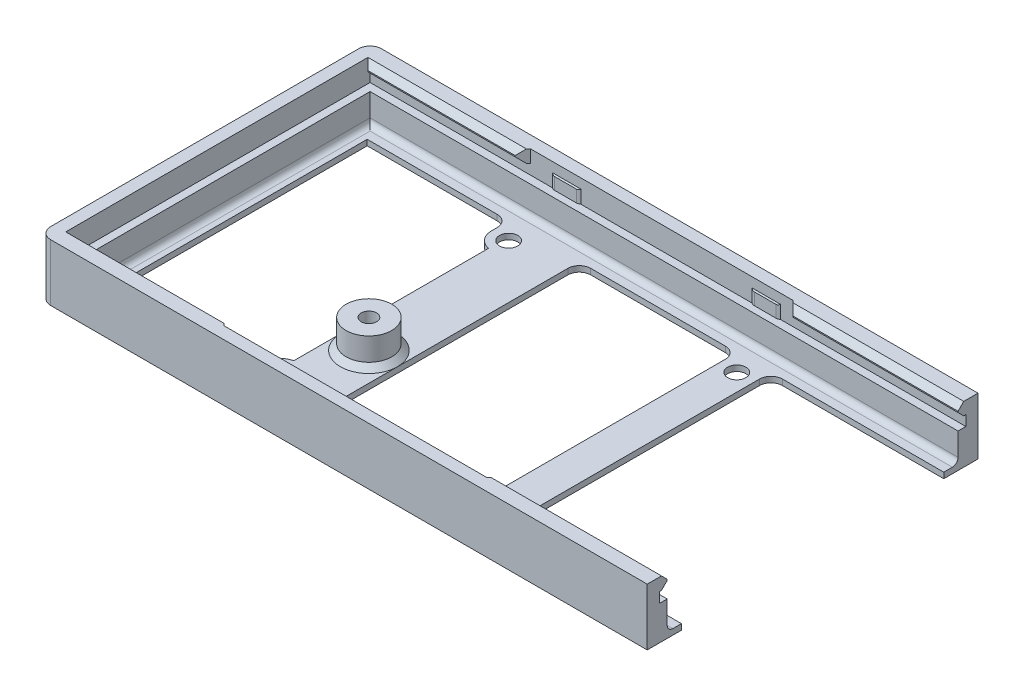
SolidWorks part; units mm, degrees
other "Cámara1"
ref_plane "Alzado" through (0, 0, 0) normal (0, 0, 1) x (1, 0, 0)
ref_plane "Planta" through (0, 0, 0) normal (0, 1, 0) x (1, 0, 0)
ref_plane "Vista lateral" through (0, 0, 0) normal (1, 0, 0) x (0, 0, -1)
sketch "Croquis1" plane through (0, 0, 0) normal (0, 1, 0) x (1, 0, 0)
  line L0 (-23, 20) -> (-23, 23)
  line L1 (47.8, -23) -> (23, -23)
  line L2 (47.8, -23) -> (47.8, 23)
  line L3 (47.8, 23) -> (23, 23)
  line L4 (-47.8, -23) -> (-47.8, 23)
  line L5 (47.8, -23) -> (-47.8, 23) construction
  line L6 (47.8, 23) -> (-47.8, -23) construction
  line L7 (53.3, -29) -> (-53.3, -29)
  line L8 (53.3, -29) -> (53.3, 29)
  line L9 (53.3, 29) -> (-53.3, 29)
  line L10 (-53.3, -29) -> (-53.3, 29)
  line L11 (53.3, -29) -> (-53.3, 29) construction
  line L12 (53.3, 29) -> (-53.3, -29) construction
  line L13 (-17, 20) -> (-17, 23)
  line L14 (-23, 23) -> (-47.8, 23)
  line L15 (0, 0) -> (0, 23) construction
  line L16 (0, 0) -> (-47.8, 0) construction
  line L17 (17, 20) -> (17, 23)
  line L18 (23, 20) -> (23, 23)
  line L19 (23, -20) -> (23, -23)
  line L20 (17, -20) -> (17, -23)
  line L21 (-17, -20) -> (-17, -23)
  line L22 (-23, -20) -> (-23, -23)
  line L23 (-23, -23) -> (-47.8, -23)
  line L24 (17, -23) -> (-17, -23)
  line L25 (17, 23) -> (-17, 23)
  circle A0 centre (-20, 20) radius 1.6
  arc A1 (-23, 20) -> (-17, 20) centre (-20, 20) ccw
  arc A2 (23, 20) -> (17, 20) centre (20, 20) cw
  circle A3 centre (20, 20) radius 1.6
  circle A4 centre (20, -20) radius 1.6
  arc A5 (23, -20) -> (17, -20) centre (20, -20) ccw
  arc A6 (-23, -20) -> (-17, -20) centre (-20, -20) cw
  circle A7 centre (-20, -20) radius 1.6
  point P0 (0, 0)
  point P6 (0, 0)
  dimension "D5" = 3.2
  dimension "D6" = 40
  dimension "D7" = 40
  dimension "D1" = 106.6
  dimension "D2" = 58
  dimension "D3" = 5.5
  dimension "D4" = 6
extrude "Saliente-Extruir1" add sketch "Croquis1" along normal blind 1
fillet "Redondeo1" radius 2 8 edges at (-23, 0.5, 23) (23, 0.5, 23) (17, 0.5, 23) (-17, 0.5, 23) (23, 0.5, -23) (17, 0.5, -23) (-17, 0.5, -23) (-23, 0.5, -23)
sketch "Croquis2" plane through (0, 1, 0) normal (0, 1, 0) x (1, 0, 0)
  line L0 (53.3, -25.5) -> (53.3, -29)
  line L1 (-53.3, 29) -> (53.3, 29)
  line L2 (-53.3, 29) -> (-53.3, -29)
  line L3 (-53.3, -29) -> (53.3, -29)
  line L4 (53.3, 29) -> (53.3, 25.5)
  line L5 (53.3, -25.5) -> (-49.8, -25.5)
  line L7 (53.3, 25.5) -> (-49.8, 25.5)
  line L8 (-49.8, -25.5) -> (-49.8, 25.5)
  point P6 (0, 0)
  dimension "D1" = 3.5
  dimension "D2" = 3.5
  dimension "D3" = 3.5
extrude "Saliente-Extruir2" add sketch "Croquis2" along normal blind 9
sketch "Croquis3" plane through (53.3, 0, 0) normal (1, 0, 0) x (0, 0, -1)
  line L1 (26.87, 6) -> (-26.87, 6)
  line L2 (26.87, 6) -> (26.87, 7.8)
  line L3 (26.87, 7.8) -> (-26.87, 7.8)
  line L4 (-26.87, 6) -> (-26.87, 7.8)
  line L5 (26.87, 6) -> (-26.87, 7.8) construction
  line L6 (26.87, 7.8) -> (-26.87, 6) construction
  line L7 (-29, 0) -> (29, 0) construction
  point P0 (0, 6.9)
  dimension "D1" = 6
  dimension "D2" = 53.74
  dimension "D3" = 1.8
extrude "Cortar-Extruir2" cut sketch "Croquis3" against normal blind 104.47
sketch "Croquis10" plane through (0, 10, 0) normal (0, 1, 0) x (1, 0, 0)
  line L0 (-53.3, 29) -> (-53.3, -29) construction
  line L1 (-49.8, -25.5) -> (-51.17, -25.5)
  line L2 (-49.8, -25.5) -> (-49.8, 25.5)
  line L3 (-49.8, 25.5) -> (-51.17, 25.5)
  line L4 (-51.17, -25.5) -> (-51.17, 25.5)
  line L5 (-49.8, -25.5) -> (-51.17, 25.5) construction
  line L6 (-49.8, 25.5) -> (-51.17, -25.5) construction
  line L7 (-51.17, -26.87) -> (-51.17, 26.87) construction
  line L8 (-51.17, -26.87) -> (-51.17, 26.87) construction
  line L11 (53.3, -25.5) -> (-49.8, -25.5) construction
  line L13 (-49.8, -25.5) -> (-49.8, 25.5) construction
  point P0 (-50.485, 0)
  point P9 (-53.3, 0)
extrude "Cortar-Extruir4" cut sketch "Croquis10" against normal up to surface (4 mm away) up to face at (1.4075, 6, 0)
chamfer "Chaflán1" distance 1 distance2 1 4 edges at (1.065, 10, 25.5) (1.065, 10, -25.5) (1.065, 7.8, -25.5) (1.065, 7.8, 25.5)
ref_plane "Plano1" through (18.3, 0, 0) normal (1, 0, 0) x (0, 0, -1)
ref_plane "Plano2" through (-16.7, 0, 0) normal (1, 0, 0) x (0, 0, -1)
sketch "Croquis4" plane through (18.3, 0, 0) normal (1, 0, 0) x (0, 0, -1)
  line L2 (-26.87, 7.8) -> (-26.87, 6)
  line L3 (-26.87, 6) -> (-26.67, 6)
  line L4 (-26.67, 7.8) -> (-26.67, 6)
  line L5 (0, 0) -> (0, 10) construction
  line L6 (-25.5, 10) -> (25.5, 10) construction
  line L12 (-26.87, 7.8) -> (-26.87, 6) construction
  line L13 (-26.5, 7.8) -> (-26.87, 7.8) construction
  line L15 (-26.87, 7.8) -> (-26.67, 7.8)
  line L16 (-26.87, 6) -> (-25.5, 6) construction
  line L17 (26.87, 7.8) -> (26.67, 7.8)
  line L18 (26.67, 7.8) -> (26.67, 6)
  line L19 (26.87, 6) -> (26.67, 6)
  line L20 (26.87, 7.8) -> (26.87, 6)
  dimension "D1" = 0.2
sketch "Croquis5" plane through (-16.7, 0, 0) normal (1, 0, 0) x (0, 0, -1)
  line L0 (0, 0) -> (0, 10) construction
  line L1 (26.5, 10) -> (-26.5, 10) construction
  line L2 (26.87, 7.8) -> (26.87, 6)
  line L3 (26.87, 6) -> (26.67, 6)
  line L4 (26.67, 6) -> (26.67, 7.8)
  line L5 (26.67, 7.8) -> (26.87, 7.8)
  line L12 (-26.67, 7.8) -> (-26.87, 7.8)
  line L13 (-26.67, 6) -> (-26.67, 7.8)
  line L14 (-26.87, 6) -> (-26.67, 6)
  line L15 (-26.87, 7.8) -> (-26.87, 6)
  line L16 (-26.67, 7.8) -> (-26.87, 7.8)
  line L17 (-26.67, 6) -> (-26.67, 7.8)
  line L18 (-26.87, 6) -> (-26.67, 6)
  line L19 (-26.87, 7.8) -> (-26.87, 6)
  dimension "D2" = 0
extrude "Saliente-Extruir4" add sketch "Croquis5" along normal mid plane 5
extrude "Saliente-Extruir3" add sketch "Croquis4" along normal mid plane 5
fillet "Redondeo5" radius 2 2 edges at (-53.3, 5, -29) (-53.3, 5, 29)
sketch "Croquis6" plane through (0, 0, 0) normal (0, -1, 0) x (1, 0, 0)
  line L0 (47.8, -23) -> (25, -23) construction
  line L1 (47.8, 23) -> (47.8, -23) construction
  line L2 (-20.61, 23) -> (-10.61, 23)
  line L3 (-20.61, 23) -> (-20.61, -23)
  line L4 (-20.61, -23) -> (-10.61, -23)
  line L5 (-10.61, 23) -> (-10.61, -23)
  line L6 (-20.61, 23) -> (-10.61, -23) construction
  line L7 (-20.61, -23) -> (-10.61, 23) construction
  line L8 (17, 23) -> (23, 23)
  line L9 (-15, 23) -> (15, 23) construction
  line L10 (17, 23) -> (17, -23)
  line L11 (17, -23) -> (23, -23)
  line L12 (23, 23) -> (23, -23)
  line L13 (17, 23) -> (23, -23) construction
  line L14 (17, -23) -> (23, 23) construction
  circle A0 centre (-15.61, 8.89) radius 1.35
  point P0 (-15.61, 0)
  point P5 (20, 0)
  point P8 (47.8, 0)
  dimension "D2" = 14.11
  dimension "D3" = 2.7
  dimension "D1" = 63.41
  dimension "D4" = 10
extrude "Saliente-Extruir5" add sketch "Croquis6" against normal up to surface (1 mm away) up to face at (20, 1, 21.6)
fillet "Redondeo6" radius 2 2 edges at (-10.61, 0.5, 23) (-10.61, 0.5, -23)
sketch "Croquis7" plane through (0, 1, 0) normal (0, 1, 0) x (1, 0, 0)
  circle A0 centre (-15.61, -8.89) radius 4
  circle A1 centre (-15.61, -8.89) radius 1.35 construction
  circle A2 centre (-15.61, -8.89) radius 1.35
  dimension "D1" = 8
extrude "Saliente-Extruir6" add sketch "Croquis7" along normal blind 5
chamfer "Chaflán2" distance 1 angle 45 1 edges at (-15.61, 1, 12.89)
fillet "Redondeo4" radius 1 8 edges at (15.8, 6.9, 26.67) (20.8, 6.9, 26.67) (-19.2, 6.9, 26.67) (-14.2, 6.9, 26.67) (-14.2, 6.9, -26.67) (-19.2, 6.9, -26.67) (15.8, 6.9, -26.67) (20.8, 6.9, -26.67)
sketch "Croquis9" plane through (0, 10, 0) normal (0, 1, 0) x (1, 0, 0)
  line L3 (-25, 26.87) -> (25, 26.87)
  line L4 (-51.17, 26.5) -> (-51.17, -26.5) construction
  line L5 (-25, -26.87) -> (25, -26.87)
  line L6 (-25, -26.87) -> (-25, 26.87)
  line L8 (25, -26.87) -> (25, 26.87)
  line L9 (-25, -26.87) -> (25, 26.87) construction
  line L10 (-25, 26.87) -> (25, -26.87) construction
  point P2 (0, 0)
  point P9 (-51.17, 0)
  dimension "D1" = 50
  dimension "D2" = 53.74
extrude "Cortar-Extruir3" cut sketch "Croquis9" against normal up to vertex (2.07 mm away)
sketch "Croquis11" plane through (0, 1, 0) normal (0, 1, 0) x (1, 0, 0)
  line L0 (0, 0) -> (-47.8, 0) construction
  line L1 (-47.8, 23) -> (-47.8, -23) construction
  line L2 (17, 0) -> (23, 0) construction
  line L3 (17, -21) -> (17, 21) construction
  line L4 (23, 21) -> (23, -21) construction
  line L5 (53.3, -25.5) -> (53.3, 25.5) construction
  line L6 (47.8, 23) -> (53.3, 23)
  line L7 (47.8, 23) -> (47.8, -23)
  line L8 (47.8, -23) -> (53.3, -23)
  line L9 (53.3, 23) -> (53.3, -23)
  line L10 (25, -23) -> (47.8, -23) construction
  circle A0 centre (-20, 20) radius 1.6
  circle A1 centre (20, -20) radius 1.6
  circle A2 centre (20, 20) radius 1.6
  circle A3 centre (-20, -20) radius 1.6
  point P19 (20, 0)
  dimension "D1" = 3.2
  dimension "D2" = 3.2
extrude "Cortar-Extruir5" cut sketch "Croquis11" against normal blind 10
fillet "Redondeo7" radius 1 3 edges at (1.75, 1, -25.5) (-49.8, 1, 0) (1.75, 1, 25.5)
sketch "Croquis12" plane through (0, 10, 0) normal (0, 1, 0) x (1, 0, 0)
  line L0 (-25, -26.5) -> (-51.17, -26.5) construction
  line L1 (-51.17, 26.5) -> (-49.17, 26.5)
  line L2 (-51.17, 26.5) -> (-51.17, -26.5)
  line L3 (-51.17, -26.5) -> (-49.17, -26.5)
  line L4 (-49.17, 26.5) -> (-49.17, -26.5)
  dimension "D1" = 2
extrude "Cortar-Extruir6" cut sketch "Croquis12" against normal up to surface (4 mm away)
chamfer "Chaflán6" distance 2 angle 45 6 edges at (-49.17, 8.9, 26.5) (-49.17, 8.9, -26.5) (25, 8.9, 26.87) (-25, 8.9, 26.87) (25, 8.9, -26.87) (-25, 8.9, -26.87)
chamfer "Chaflán8" distance 0.5 angle 45 4 edges at (18.3, 7.8, -26.87) (-16.7, 7.8, -26.87) (-16.7, 7.8, 26.87) (18.3, 7.8, 26.87)
